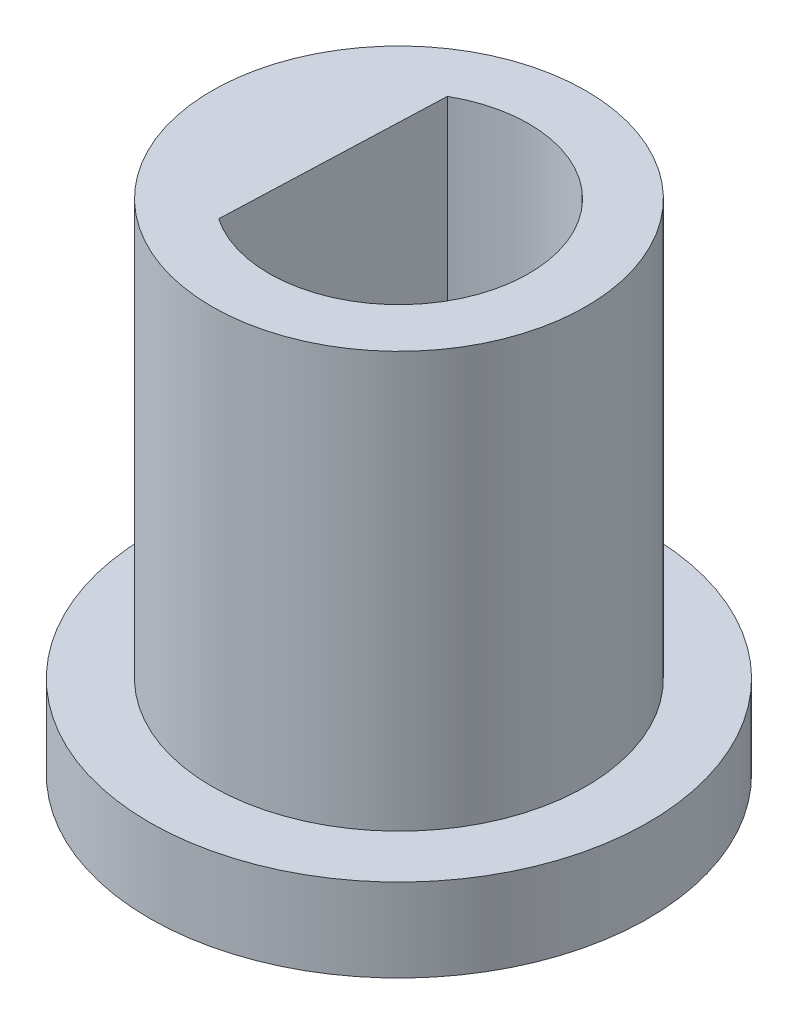
SolidWorks part; units mm, degrees
ref_plane "Front Plane" through (0, 0, 0) normal (0, 0, 1) x (1, 0, 0)
ref_plane "Top Plane" through (0, 0, 0) normal (0, 1, 0) x (1, 0, 0)
ref_plane "Right Plane" through (0, 0, 0) normal (1, 0, 0) x (0, 0, -1)
sketch "Sketch1" plane through (0, 0, 0) normal (0, 1, 0) x (1, 0, 0)
  circle A0 centre (0, 0) radius 6
  dimension "D1" = 12
extrude "Boss-Extrude1" add sketch "Sketch1" along normal blind 2
sketch "Sketch2" plane through (0, 2, 0) normal (0, 1, 0) x (1, 0, 0)
  circle A0 centre (0, 0) radius 4.5
  dimension "D1" = 9
extrude "Boss-Extrude2" add sketch "Sketch2" along normal blind 10
sketch "Sketch3" plane through (0, 0, 0) normal (0, -1, 0) x (-1, 0, 0)
  line L1 (2.625, 2.625) -> (-2.625, 2.625)
  line L2 (2.625, 2.625) -> (2.625, -2.625)
  line L3 (2.625, -2.625) -> (-2.625, -2.625)
  line L4 (-2.625, 2.625) -> (-2.625, -2.625)
  line L5 (2.625, 2.625) -> (-2.625, -2.625) construction
  line L6 (2.625, -2.625) -> (-2.625, 2.625) construction
  point P0 (0, 0)
  dimension "D1" = 5.25
  dimension "D2" = 5.25
extrude "Cut-Extrude1" cut sketch "Sketch3" against normal blind 2
sketch "Sketch4" plane through (0, 12, 0) normal (0, 1, 0) x (1, 0, 0)
  circle A0 centre (0, 0) radius 3.125
  dimension "D1" = 6.25
extrude "Cut-Extrude2" cut sketch "Sketch4" against normal blind 8
sketch "Sketch5" plane through (0, 4, 0) normal (0, 1, 0) x (1, 0, 0)
  line L0 (-1.5486, 2.7143) -> (-1.749, -2.5897)
  circle A0 centre (0, 0) radius 3.125 construction
  circle A2 centre (0, 0) radius 3.125
  circle M2 centre (0, 0) radius 3.125
  dimension "D1" = 1.65
extrude "Boss-Extrude3" add sketch "Sketch5" along normal up to surface (8 mm away) contours L0 M2 region at (-2.2522, 4, -0.0851) up to face at (0, 12, 3.125)
